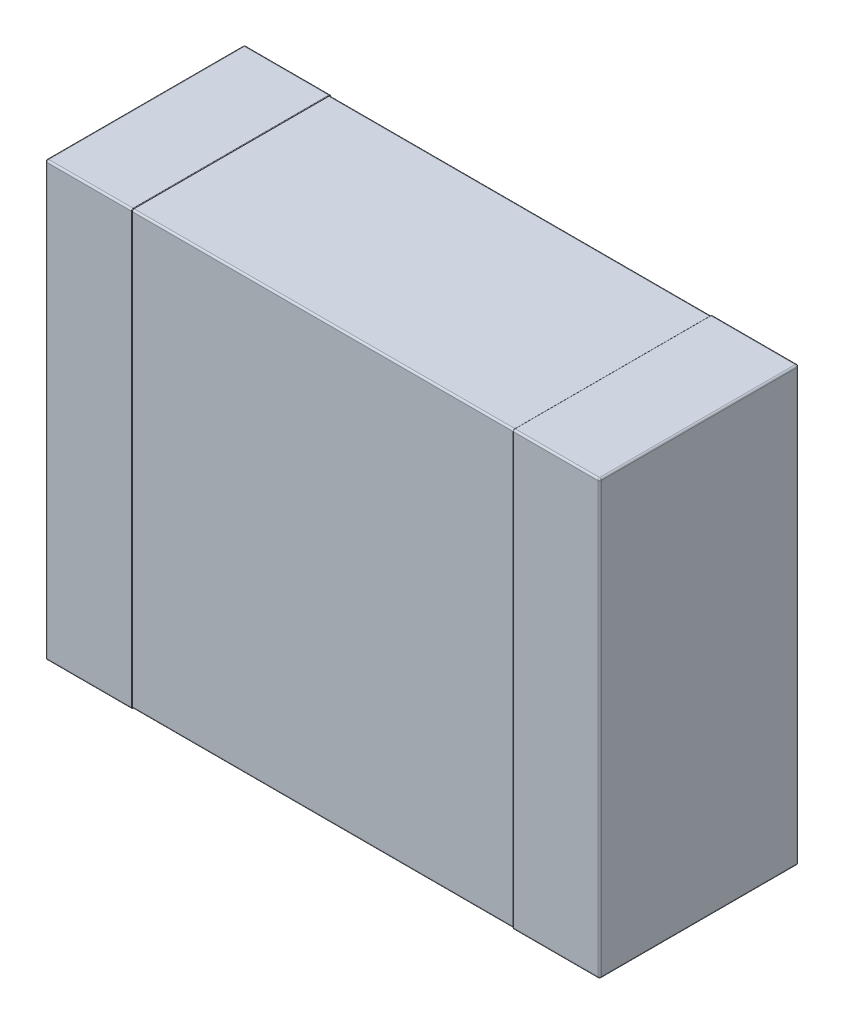
SolidWorks part; units mm, degrees
ref_plane "Top Plane" through (0, 0, 0) normal (0, 0, 1) x (1, 0, 0)
ref_plane "Front Plane" through (0, 0, 0) normal (0, 1, 0) x (1, 0, 0)
ref_plane "Side Plane" through (0, 0, 0) normal (1, 0, 0) x (0, 0, -1)
sketch "Sketch1" plane through (0, 0, 0) normal (0, 0, 1) x (1, 0, 0)
  line L1 (-1.6, 1.25) -> (1.6, 1.25)
  line L2 (-1.6, 1.25) -> (-1.6, -1.25)
  line L3 (-1.6, -1.25) -> (1.6, -1.25)
  line L4 (1.6, 1.25) -> (1.6, -1.25)
  dimension "D1" = 3.2
  dimension "D2" = 1.6
  dimension "D3" = 2.5
  dimension "D4" = 1.25
extrude "All body" add sketch "Sketch1" along normal blind 1.15
sketch "Sketch2" plane through (0, 0, 0) normal (1, 0, 0) x (0, 0, -1)
  line L14 (-0.003, 1.247) -> (-1.147, 1.247)
  line L15 (-0.003, -1.247) -> (-0.003, 1.247)
  line L16 (-1.147, -1.247) -> (-0.003, -1.247)
  line L17 (-1.147, 1.247) -> (-1.147, -1.247)
  line L18 (-0.003, 1.247) -> (-1.147, 1.247)
  line L19 (-0.003, -1.247) -> (-0.003, 1.247)
  line L20 (-1.147, -1.247) -> (-0.003, -1.247)
  line L21 (-1.147, 1.247) -> (-1.147, -1.247)
  dimension "D1" = 0.003
extrude "Cut out the body for pin" cut sketch "Sketch2" against normal blind 1.1 and the other way blind 1.1 flip side to cut
fillet "Body fillet" radius 0.01 4 edges at (0, 1.247, 0.003) (0, 1.247, 1.147) (0, -1.247, 0.003) (0, -1.247, 1.147)
fillet "Pin fillet a" radius 0.01 16 edges at (1.6, -1.25, 0.575) (1.6, 0, 1.15) (1.6, 1.25, 0.575) (1.6, 0, 0) (-1.6, 1.25, 0.575) (-1.6, 0, 1.15) (-1.6, -1.25, 0.575) (-1.6, 0, 0) (1.35, 1.25, 1.15) (1.35, -1.25, 1.15) (1.35, -1.25, 0) (1.35, 1.25, 0) (-1.35, 1.25, 0) (-1.35, -1.25, 0) (-1.35, 1.25, 1.15) (-1.35, -1.25, 1.15)
fillet "Pin fillet b" radius 0.003 16 edges at (1.1, -1.2471, 1.1471) (1.1, -1.25, 0.575) (1.1, -1.2471, 0.0029) (1.1, 0, 0) (1.1, 1.2471, 0.0029) (1.1, 1.25, 0.575) (1.1, 1.2471, 1.1471) (-1.1, -1.2471, 1.1471) (-1.1, -1.25, 0.575) (-1.1, -1.2471, 0.0029) (-1.1, 0, 0) (-1.1, 1.2471, 0.0029) (-1.1, 1.25, 0.575) (-1.1, 1.2471, 1.1471) (1.1, 0, 1.15) (-1.1, 0, 1.15)
